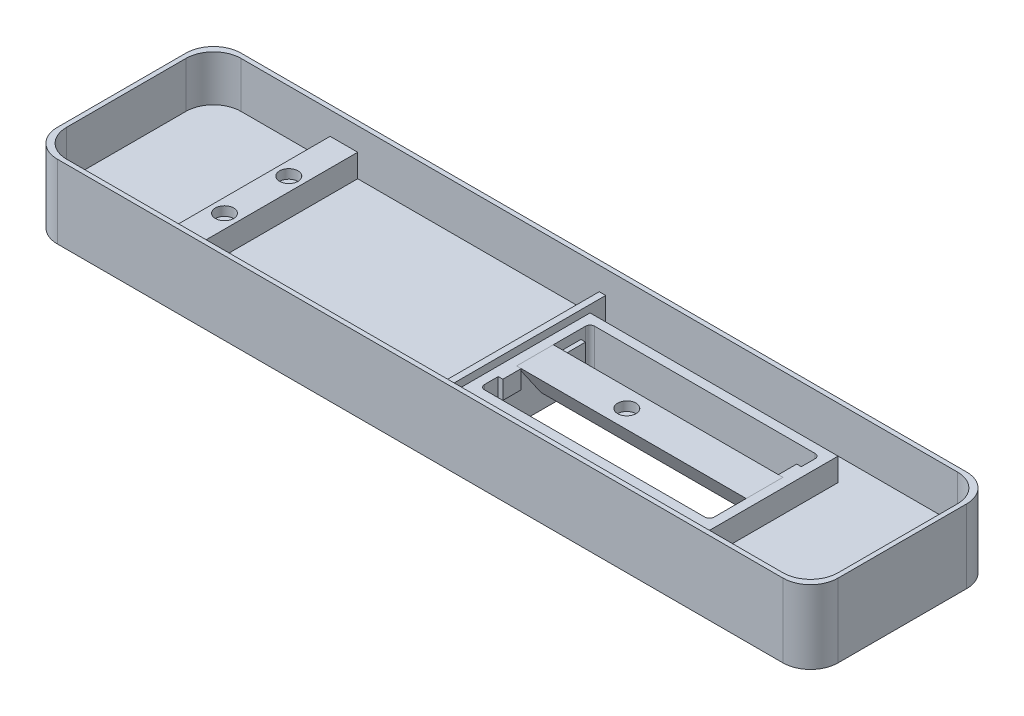
SolidWorks part; units mm, degrees
material "PVB"
ref_plane "Front Plane" through (0, 0, 0) normal (0, 0, 1) x (1, 0, 0)
ref_plane "Top Plane" through (0, 0, 0) normal (0, 1, 0) x (1, 0, 0)
ref_plane "Right Plane" through (0, 0, 0) normal (1, 0, 0) x (0, 0, -1)
ref_axis "X-axis" through (-88.99, 0, 0) along (1, 0, 0)
ref_axis "Y-axis" through (0, 55, 0) along (0, -1, 0)
ref_axis "Z-axis" through (0, 0, -88.99) along (0, 0, 1)
sketch "Sketch1" plane through (0, 0, 0) normal (0, 1, 0) x (1, 0, 0)
  line L1 (-107.95, 25.4) -> (107.95, 25.4)
  line L2 (-107.95, 25.4) -> (-107.95, -25.4)
  line L3 (-107.95, -25.4) -> (107.95, -25.4)
  line L4 (107.95, 25.4) -> (107.95, -25.4)
  line L5 (-107.95, 25.4) -> (107.95, -25.4) construction
  line L6 (-107.95, -25.4) -> (107.95, 25.4) construction
  point P0 (0, 0)
  dimension "D1" = 215.9
  dimension "D2" = 50.8
extrude "Boss-Extrude1" add sketch "Sketch1" along normal mid plane 20.32
sketch "Sketch3" plane through (0, 10.16, 0) normal (0, 1, 0) x (1, 0, 0)
  line L0 (-107.95, 25.4) -> (-107.95, -25.4) construction
  line L1 (-106.68, 24.13) -> (106.68, 24.13)
  line L2 (-106.68, 24.13) -> (-106.68, -24.13)
  line L3 (-106.68, -24.13) -> (106.68, -24.13)
  line L4 (106.68, 24.13) -> (106.68, -24.13)
  line L5 (-106.68, 24.13) -> (106.68, -24.13) construction
  line L6 (-106.68, -24.13) -> (106.68, 24.13) construction
  line L8 (107.95, 25.4) -> (-107.95, 25.4) construction
  point P0 (0, 0)
  dimension "D1" = 1.27
  dimension "D2" = 1.27
extrude "Cut-Extrude1" cut sketch "Sketch3" against normal blind 12.7
fillet "Fillet3" radius 7.62 8 edges at (106.68, 3.81, 24.13) (106.68, 3.81, -24.13) (-106.68, 3.81, 24.13) (-106.68, 3.81, -24.13) (-107.95, 0, 25.4) (107.95, 0, -25.4) (107.95, 0, 25.4) (-107.95, 0, -25.4)
sketch "Sketch4" plane through (0, -2.54, 0) normal (0, 1, 0) x (1, 0, 0)
  line L0 (99.06, 24.13) -> (-99.06, 24.13) construction
  line L1 (-74.422, 24.13) -> (-66.802, 24.13)
  line L2 (-74.422, 24.13) -> (-74.422, -24.13)
  line L3 (-74.422, -24.13) -> (-66.802, -24.13)
  line L4 (-66.802, 24.13) -> (-66.802, -24.13)
  line L5 (-99.06, -24.13) -> (99.06, -24.13) construction
  line L6 (-107.95, 17.78) -> (-107.95, -17.78) construction
  line L7 (0, 24.13) -> (1.778, 24.13)
  line L8 (0, 24.13) -> (0, -24.13)
  line L9 (0, -24.13) -> (1.778, -24.13)
  line L10 (1.778, 24.13) -> (1.778, -24.13)
  point P12 (-70.612, -24.13)
  dimension "D1" = 1.778
  dimension "D2" = 7.62
  dimension "D3" = 37.338
extrude "Boss-Extrude2" add sketch "Sketch4" along normal blind 6.35
sketch "Sketch5" plane through (0, -2.54, 0) normal (0, 1, 0) x (1, 0, 0)
  line L0 (107.95, -17.78) -> (107.95, 17.78) construction
  line L1 (3.81, 17.78) -> (72.39, 17.78)
  line L2 (3.81, 17.78) -> (3.81, -17.78)
  line L3 (3.81, -17.78) -> (72.39, -17.78)
  line L4 (72.39, 17.78) -> (72.39, -17.78)
  line L5 (3.81, 17.78) -> (72.39, -17.78) construction
  line L6 (3.81, -17.78) -> (72.39, 17.78) construction
  point P0 (38.1, 0)
  dimension "D1" = 35.56
  dimension "D2" = 35.56
  dimension "D3" = 68.58
extrude "Boss-Extrude3" add sketch "Sketch5" along normal blind 6.35
sketch "Sketch9" plane through (0, -2.54, 0) normal (0, 1, 0) x (1, 0, 0)
  line L0 (3.81, 17.78) -> (3.81, -17.78) construction
  line L1 (6.35, 15.24) -> (69.85, 15.24)
  line L2 (6.35, 15.24) -> (6.35, -15.24)
  line L3 (6.35, -15.24) -> (69.85, -15.24)
  line L4 (69.85, 15.24) -> (69.85, -15.24)
  line L5 (6.35, 15.24) -> (69.85, -15.24) construction
  line L6 (6.35, -15.24) -> (69.85, 15.24) construction
  line L7 (72.39, -17.78) -> (72.39, 17.78) construction
  line L8 (3.81, -17.78) -> (72.39, -17.78) construction
  line L9 (72.39, 17.78) -> (3.81, 17.78) construction
  point P0 (38.1, 0)
  dimension "D1" = 2.54
  dimension "D2" = 2.54
  dimension "D3" = 2.54
  dimension "D4" = 2.54
extrude "Cut-Extrude2" cut sketch "Sketch9" against normal through all both and the other way through all
sketch "Sketch10" plane through (0, 3.81, 0) normal (0, 1, 0) x (1, 0, 0)
  line L0 (6.35, -5.08) -> (69.85, -5.08)
  line L1 (6.35, 15.24) -> (6.35, -15.24) construction
  line L2 (69.85, -15.24) -> (69.85, 15.24) construction
  line L3 (69.85, -5.08) -> (69.85, 5.08)
  line L4 (69.85, 5.08) -> (6.35, 5.08)
  line L5 (6.35, 5.08) -> (6.35, -5.08)
  point P6 (6.35, 0)
  dimension "D1" = 5.08
extrude "Boss-Extrude4" add sketch "Sketch10" against normal blind 6.35 draft 28 from offset 0
sketch "Sketch11" plane through (6.35, 0, 0) normal (1, 0, 0) x (0, 0, -1)
  line L0 (-25.4, -10.16) -> (-25.4, 10.16) construction
  line L1 (-10.16, 3.81) -> (-5.08, 3.81)
  line L2 (-10.16, 3.81) -> (-10.16, -1.27)
  line L3 (-10.16, -1.27) -> (-5.08, -1.27)
  line L4 (-5.08, 3.81) -> (-5.08, -1.27)
  line L5 (7.62, 1.27) -> (12.7, 1.27)
  line L6 (7.62, 1.27) -> (7.62, -3.81)
  line L7 (7.62, -3.81) -> (12.7, -3.81)
  line L8 (12.7, 1.27) -> (12.7, -3.81)
  line L11 (-17.78, 10.16) -> (17.78, 10.16) construction
  dimension "D1" = 5.08
  dimension "D2" = 5.08
  dimension "D3" = 12.7
  dimension "D4" = 15.24
  dimension "D5" = 5.08
  dimension "D6" = 5.08
  dimension "D7" = 6.35
extrude "Boss-Extrude5" add sketch "Sketch11" along normal blind 1.27
sketch "Sketch13" plane through (69.85, 0, 0) normal (-1, 0, 0) x (0, 0, 1)
  line L1 (-10.16, 3.81) -> (-5.08, 3.81)
  line L2 (-10.16, 3.81) -> (-10.16, -1.27)
  line L3 (-10.16, -1.27) -> (-5.08, -1.27)
  line L4 (-5.08, 3.81) -> (-5.08, -1.27)
  line L5 (7.62, 1.27) -> (12.7, 1.27)
  line L6 (7.62, 1.27) -> (7.62, -3.81)
  line L7 (7.62, -3.81) -> (12.7, -3.81)
  line L8 (12.7, 1.27) -> (12.7, -3.81)
  line L9 (-17.78, 10.16) -> (17.78, 10.16) construction
  line L10 (-25.4, -10.16) -> (-25.4, 10.16) construction
  dimension "D1" = 5.08
  dimension "D2" = 5.08
  dimension "D3" = 12.7
  dimension "D4" = 15.24
  dimension "D5" = 5.08
  dimension "D6" = 5.08
  dimension "D7" = 6.35
extrude "Boss-Extrude6" add sketch "Sketch13" along normal blind 1.27
sketch "Sketch16" plane through (69.85, 0, 0) normal (-1, 0, 0) x (0, 0, 1)
  line L1 (-5.08, -7.62) -> (-5.08, -2.54)
  line L2 (-5.08, -2.54) -> (5.08, -2.54)
  line L3 (5.08, -2.54) -> (5.08, -7.62)
  line L4 (5.08, -7.62) -> (-5.08, -7.62)
extrude "Cut-Extrude3" cut sketch "Sketch16" against normal blind 1.27
fillet "Fillet4" radius 1.27 4 edges at (69.85, -3.175, -15.24) (69.85, -3.175, 15.24) (6.35, -3.175, 15.24) (6.35, -3.175, -15.24)
sketch "Sketch19" plane through (0, -10.16, 0) normal (0, -1, 0) x (1, 0, 0)
  line L0 (71.12, -5.08) -> (71.12, 5.08) construction
  circle A0 centre (71.12, 0) radius 5.08
extrude "Cut-Extrude5" cut sketch "Sketch19" against normal blind 0.508
sketch "Sketch21" plane through (6.35, 0, 0) normal (1, 0, 0) x (0, 0, -1)
  line L0 (-15.24, -10.16) -> (-15.24, 3.81) construction
  line L1 (-8.89, -10.033) -> (-12.7, -10.033)
  line L2 (-8.89, -10.033) -> (-8.89, -9.652)
  line L3 (-8.89, -9.652) -> (-12.7, -9.652)
  line L4 (-12.7, -10.033) -> (-12.7, -9.652)
  line L5 (8.89, -10.033) -> (12.7, -10.033)
  line L6 (8.89, -10.033) -> (8.89, -9.652)
  line L7 (8.89, -9.652) -> (12.7, -9.652)
  line L8 (12.7, -10.033) -> (12.7, -9.652)
  line L9 (15.24, 3.81) -> (15.24, -10.16) construction
  line L10 (13.97, -10.16) -> (-13.97, -10.16) construction
  dimension "D1" = 3.81
  dimension "D2" = 0.381
  dimension "D3" = 2.54
  dimension "D4" = 2.54
  dimension "D5" = 0.127
extrude "Cut-Extrude7" cut sketch "Sketch21" against normal blind 3.937
sketch "Sketch24" plane through (0, 3.81, 0) normal (0, 1, 0) x (1, 0, 0)
  line L0 (-100.33, -25.4) -> (100.33, -25.4) construction
  line L1 (100.33, 25.4) -> (-100.33, 25.4) construction
  circle A0 centre (-70.612, -8.89) radius 2.54
  circle A1 centre (-70.612, 8.89) radius 2.54
  dimension "D1" = 5.08
  dimension "D2" = 5.08
  dimension "D3" = 16.51
  dimension "D4" = 16.51
extrude "Cut-Extrude11" cut sketch "Sketch24" against normal blind 2.54
sketch "Sketch25" plane through (0, 3.81, 0) normal (0, 1, 0) x (1, 0, 0)
  line L0 (107.95, -17.78) -> (107.95, 17.78) construction
  line L1 (-70.612, 8.89) -> (-70.612, -8.89) construction
  circle A0 centre (31.75, 0) radius 2.54
  dimension "D1" = 76.2
  dimension "D2" = 5.08
extrude "Cut-Extrude12" cut sketch "Sketch25" against normal blind 2.54
